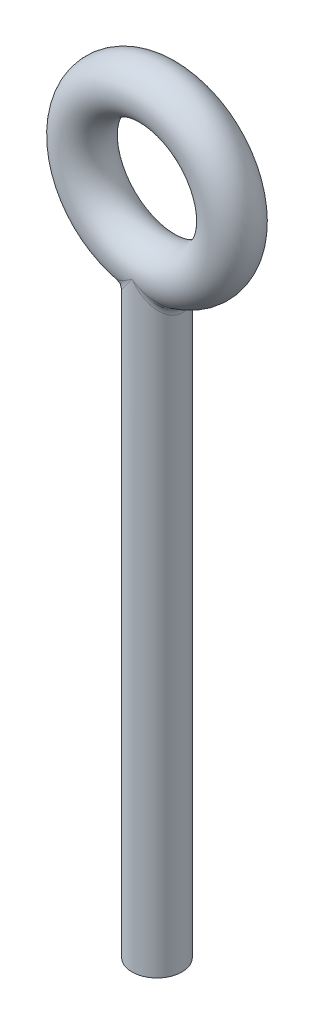
SolidWorks part; units mm, degrees
ref_plane "Front Plane" through (0, 0, 0) normal (0, 0, 1) x (1, 0, 0)
ref_plane "Top Plane" through (0, 0, 0) normal (0, 1, 0) x (1, 0, 0)
ref_plane "Right Plane" through (0, 0, 0) normal (1, 0, 0) x (0, 0, -1)
sketch "Sketch1" plane through (0, 0, 0) normal (0, 0, 1) x (1, 0, 0)
  circle A0 centre (0, 0) radius 19.05
  dimension "D1" = 38.1
sketch "Sketch2" plane through (0, 0, 0) normal (1, 0, 0) x (0, 0, -1)
  circle A0 centre (0, 19.05) radius 6.35
  dimension "D1" = 12.7
ref_axis "Axis1" through (0, 0, -88.99) along (0, 0, 1)
revolve "Revolve1" add sketch "Sketch2" angle 360 about axis through (0, 0, -88.99) along (0, 0, 1)
ref_plane "Plane1" through (0, -19.05, 0) normal (0, 1, 0) x (-1, 0, 0)
sketch "Sketch3" plane through (0, -19.05, 0) normal (0, 1, 0) x (-1, 0, 0)
  circle A0 centre (0, 0) radius 6.35
  dimension "D1" = 12.7
extrude "Boss-Extrude1" add sketch "Sketch3" against normal blind 152.4
fillet "Fillet1" radius 2.54 2 edges at (6.3426, -24.5877, 0.3062) (-6.3426, -24.5877, -0.3062)
